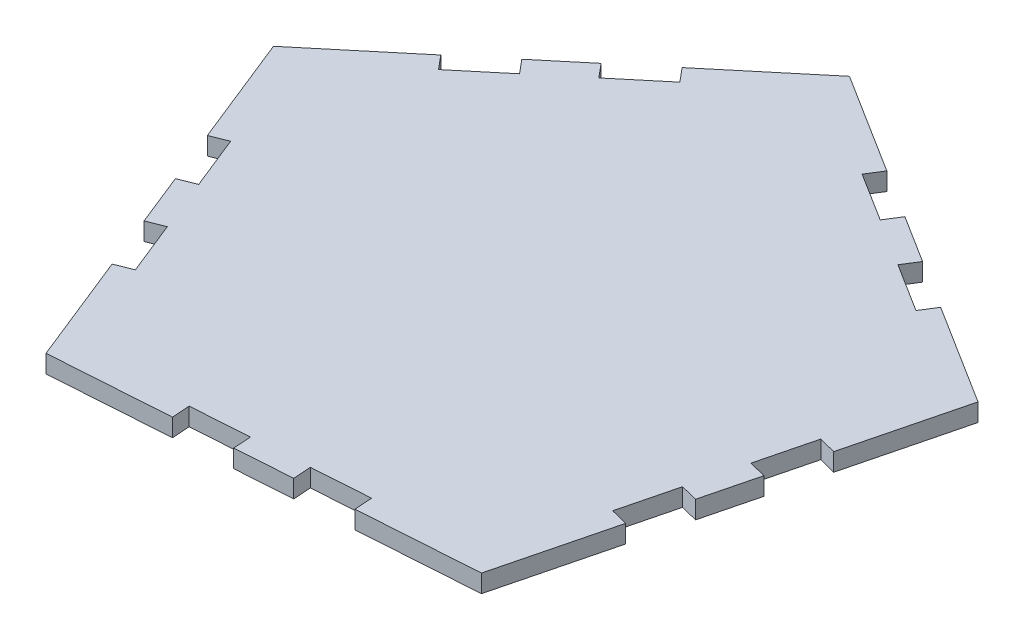
SolidWorks part; units mm, degrees
ref_plane "Front Plane" through (0, 0, 0) normal (0, 0, 1) x (1, 0, 0)
ref_plane "Top Plane" through (0, 0, 0) normal (0, 1, 0) x (1, 0, 0)
ref_plane "Right Plane" through (0, 0, 0) normal (1, 0, 0) x (0, 0, -1)
sketch "Sketch1" plane through (0, 0, 0) normal (0, 1, 0) x (1, 0, 0)
  line L1 (-59.9258, 15.1181) -> (-32.8962, -52.3211)
  line L2 (-32.8962, -52.3211) -> (39.5948, -47.4543)
  line L3 (39.5948, -47.4543) -> (57.3672, 22.9927)
  line L4 (57.3672, 22.9927) -> (-4.14, 61.6646)
  line L5 (-4.14, 61.6646) -> (-59.9258, 15.1181)
  circle A0 centre (0, 0) radius 50 construction
  dimension "D1" = 100
extrude "Boss-Extrude1" add sketch "Sketch1" along normal blind 3.18
sketch "Sketch2" plane through (0, 0, 0) normal (0, -1, 0) x (1, 0, 0)
  line L0 (-52.0733, 4.474) -> (-49.1216, 3.2909)
  line L1 (-52.0733, 4.474) -> (-48.2712, 13.9604)
  line L2 (-49.1216, 3.2909) -> (-45.3194, 12.7774)
  line L3 (-48.2712, 13.9604) -> (-45.3194, 12.7774)
  line L4 (-59.9258, -15.1181) -> (-32.8962, 52.3211) construction
  line L5 (-44.5509, 23.2426) -> (-40.7487, 32.729)
  line L6 (-44.5509, 23.2426) -> (-41.5991, 22.0596)
  line L7 (-40.7487, 32.729) -> (-37.797, 31.546)
  line L8 (-41.5991, 22.0596) -> (-37.797, 31.546)
  line L9 (-46.411, 18.6015) -> (-19.2439, 7.7129) construction
  dimension "D1" = 3.18
  dimension "D2" = 10.22
  dimension "D3" = 10
extrude "Cut-Extrude1" cut sketch "Sketch2" against normal through all
ref_axis "Axis1" through (0, 3.339, 0) along (0, -1, 0)
pattern_circular "CirPattern1" count 5 over 360 about axis through (0, 3.339, 0) along (0, -1, 0) of "Cut-Extrude1"
sketch "Sketch3" [suppressed] plane through (0, 0, 0) normal (0, -1, 0) x (-1, 0, 0)
  line L0 (0, 0) -> (53.7084, -21.5263) construction
equation "\"kerf\"= .22mm"
equation "\"tabWidth\"= 10 + \"kerf\" "
equation "\"tabSeperation\" = 10  "
equation "\"tabThickness\"= 3.18"
equation "\"D2@Sketch2\"=\"tabWidth\""
equation "\"D3@Sketch2\"=\"tabSeperation\""
equation "\"D1@Sketch2\"=\"tabThickness\""
equation "\"tabLength\" = \"kerf\" + 12"
